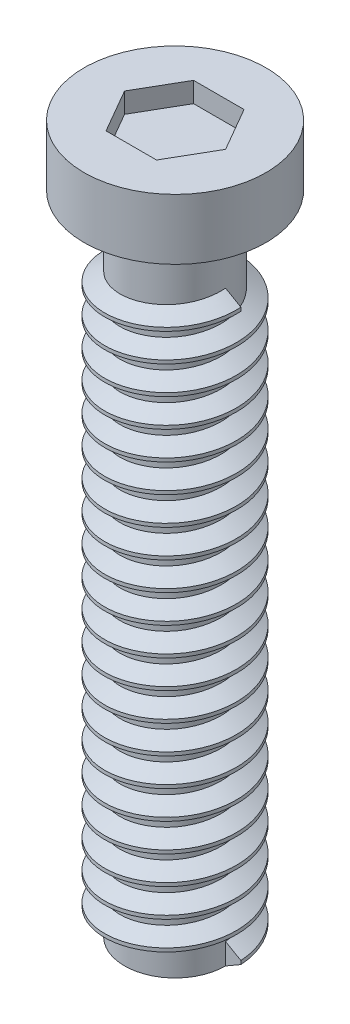
SolidWorks part; units mm, degrees
ref_plane "Front Plane" through (0, 0, 0) normal (0, 0, 1) x (1, 0, 0)
ref_plane "Top Plane" through (0, 0, 0) normal (0, 1, 0) x (1, 0, 0)
ref_plane "Right Plane" through (0, 0, 0) normal (1, 0, 0) x (0, 0, -1)
sketch "Sketch1" plane through (0, 0, 0) normal (0, 1, 0) x (1, 0, 0)
  circle A0 centre (0, 0) radius 1.25
  dimension "D1" = 2.5
extrude "Boss-Extrude1" add sketch "Sketch1" along normal blind 16
sketch "Sketch4" plane through (0, 16, 0) normal (0, 1, 0) x (1, 0, 0)
  circle A0 centre (0, 0) radius 2.25
  dimension "D1" = 4.5
extrude "Boss-Extrude2" add sketch "Sketch4" along normal blind 1.5
sketch "Sketch5" plane through (0, 17.5, 0) normal (0, 1, 0) x (1, 0, 0)
  line L1 (1.25, 0) -> (0.625, 1.0825)
  line L2 (0.625, 1.0825) -> (-0.625, 1.0825)
  line L3 (-0.625, 1.0825) -> (-1.25, 0)
  line L4 (-1.25, 0) -> (-0.625, -1.0825)
  line L5 (-0.625, -1.0825) -> (0.625, -1.0825)
  line L6 (0.625, -1.0825) -> (1.25, 0)
  circle A0 centre (0, 0) radius 1.0825 construction
  dimension "D1" = 1.25
extrude "Cut-Extrude1" cut sketch "Sketch5" against normal blind 0.5
thread "Thread1" pitch 0.7 method extrude profile "Thread Profile1" start angle 0, offset 0, length 14, pitch 0.7, diameter 2.5
ref_plane "Plane1" through (1.25, 0, 0) normal (0, 0, 1) x (1, 0, 0)
sketch "Thread Profile1" plane through (1.25, 0, 0) normal (0, 0, 1) x (1, 0, 0)
  line L0 (0, 0) -> (0, 0.7) construction
  line L1 (0, 0) -> (0.3789, 0.2187)
  line L2 (0.3789, 0.2187) -> (0.3789, 0.3062)
  line L3 (0.3789, 0.3062) -> (0, 0.525)
  line L4 (0.3789, 0.2625) -> (0, 0.2625) construction
  line L11 (0, 0) -> (0, 0.525)
  point P2 (0, 0)
  dimension "Pitch" = 0.7
  dimension "Profile_Angle" = 60
  dimension "Profile_Land" = 0.0875
  dimension "Profile_Height" = 0.3789
